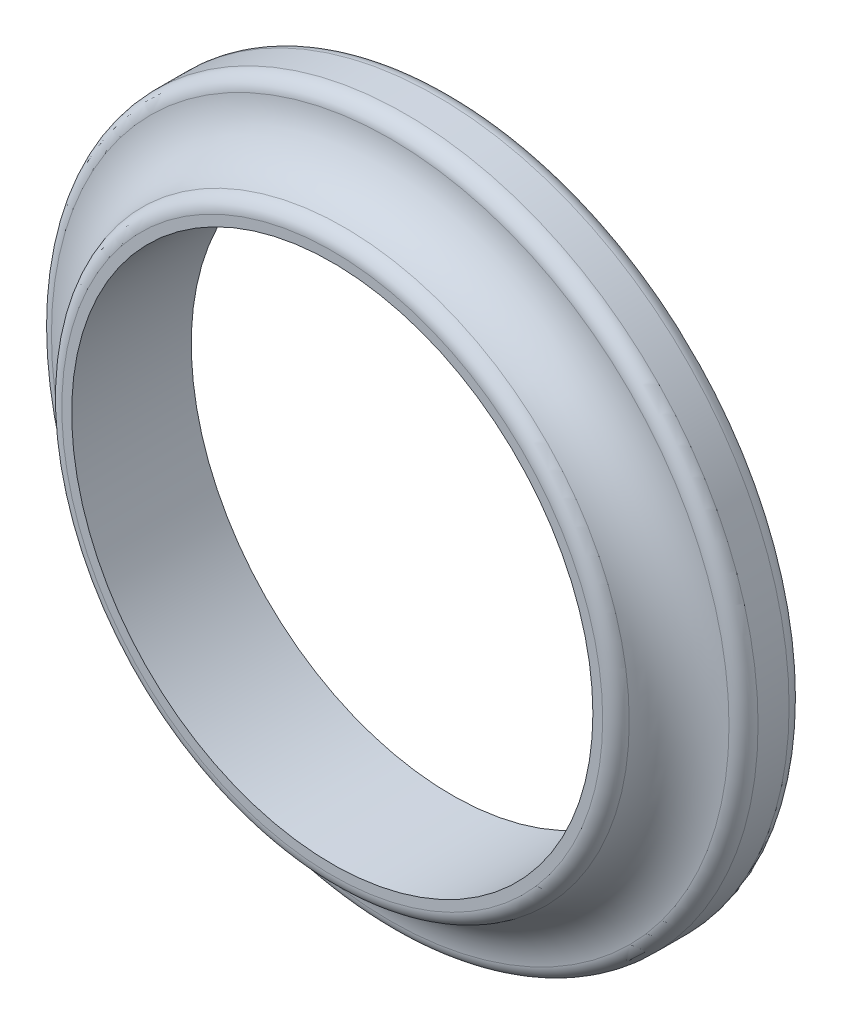
SolidWorks part; units mm, degrees
ref_plane "Front Plane" through (0, 0, 0) normal (0, 0, 1) x (1, 0, 0)
ref_plane "Top Plane" through (0, 0, 0) normal (0, 1, 0) x (1, 0, 0)
ref_plane "Right Plane" through (0, 0, 0) normal (1, 0, 0) x (0, 0, -1)
sketch "Sketch1" plane through (0, 0, 0) normal (0, 0, 1) x (1, 0, 0)
  circle A0 centre (0, 0) radius 23
  dimension "D1" = 46
extrude "Boss-Extrude1" add sketch "Sketch1" along normal blind 4
sketch "Sketch2" plane through (0, 0, 4) normal (0, 0, 1) x (1, 0, 0)
  circle A0 centre (0, 0) radius 17
  dimension "D1" = 34
extrude "Cut-Extrude1" cut sketch "Sketch2" against normal through all both and the other way through all
sketch "Sketch3" plane through (0, 0, 4) normal (0, 0, 1) x (1, 0, 0)
  circle A0 centre (0, 0) radius 18.5
  circle A1 centre (0, 0) radius 17 construction
  circle A2 centre (0, 0) radius 17
  dimension "D1" = 37
extrude "Boss-Extrude2" add sketch "Sketch3" along normal blind 3.8
fillet "Fillet1" radius 4 1 edges at (18.5, 0, 4)
fillet "Fillet2" radius 1 1 edges at (18.5, 0, 7.8)
fillet "Fillet3" radius 1 2 edges at (23, 0, 0) (23, 0, 4)
